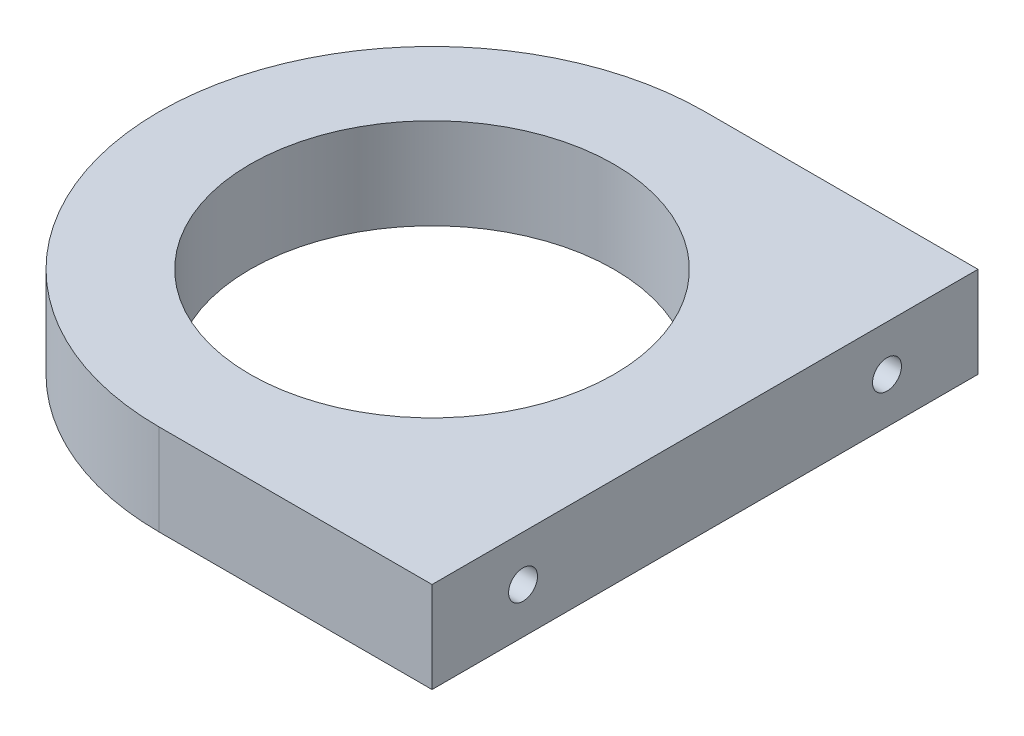
SolidWorks part; units mm, degrees
material "6061-T6 (SS)"
ref_plane "Front Plane" through (0, 0, 0) normal (0, 0, 1) x (1, 0, 0)
ref_plane "Top Plane" through (0, 0, 0) normal (0, 1, 0) x (1, 0, 0)
ref_plane "Right Plane" through (0, 0, 0) normal (1, 0, 0) x (0, 0, -1)
sketch "Sketch1" plane through (0, 0, 0) normal (0, 1, 0) x (1, 0, 0)
  line L1 (-38.1, -38.1) -> (38.1, -38.1)
  line L2 (-38.1, -38.1) -> (-38.1, 38.1)
  line L3 (-38.1, 38.1) -> (38.1, 38.1)
  line L4 (38.1, -38.1) -> (38.1, 38.1)
  line L5 (-38.1, -38.1) -> (38.1, 38.1) construction
  line L6 (-38.1, 38.1) -> (38.1, -38.1) construction
  point P0 (0, 0)
  dimension "D1" = 76.2
  dimension "D2" = 76.2
extrude "Boss-Extrude1" add sketch "Sketch1" along normal blind 12.7
sketch "Sketch2" plane through (38.1, 0, 0) normal (1, 0, 0) x (0, 0, -1)
  line L0 (-38.1, 0) -> (38.1, 0) construction
  point P0 (-25.4, 6.35)
  point P1 (25.4, 6.35)
  dimension "D1" = 25.4
  dimension "D2" = 25.4
  dimension "D3" = 6.35
hole_wizard "#10-32 Tapped Hole1" positions "Sketch4" profile "Sketch5" tap size "#10-32" standard "ANSI Inch"
sketch "Sketch4" plane through (38.1, 0, 0) normal (1, 0, 0) x (0, 0, -1)
  point P0 (-25.4, 6.35)
  point P3 (25.4, 6.35)
sketch "Sketch5" plane through (38.1, 6.35, 25.4) normal (0, 1, 0) x (0, 0, -1)
  line L0 (0, 0) -> (0, 10.8653)
  line L1 (0, 10.8653) -> (2.0193, 9.652)
  line L2 (2.0193, 9.652) -> (2.0193, 0)
  line L5 (2.0193, 0) -> (0, 0)
  line L10 (0, 10.8653) -> (-2.0193, 9.652) construction
  line L11 (0, -6.35) -> (0, 107.95) construction
  dimension "Tap Drill Dia." = 4.0386
  dimension "Tap Drill Depth" = 9.652
  dimension "Drill Angle" = 118
cosmetic thread "Hole Thread1" parameters "D1"=6.35, "D2"=4.826
cosmetic thread "Hole Thread2" parameters "D1"=6.35, "D2"=4.826
sketch "Sketch9" plane through (0, 12.7, 0) normal (0, 1, 0) x (1, 0, 0)
  circle A0 centre (0, 0) radius 25.4
  dimension "D1" = 50.8
extrude "Cut-Extrude2" cut sketch "Sketch9" against normal through all
fillet "Fillet1" radius 38.1 2 edges at (-38.1, 6.35, -38.1) (-38.1, 6.35, 38.1)
equation "\"D2@Sketch1\"=\"D1@Sketch1\""
